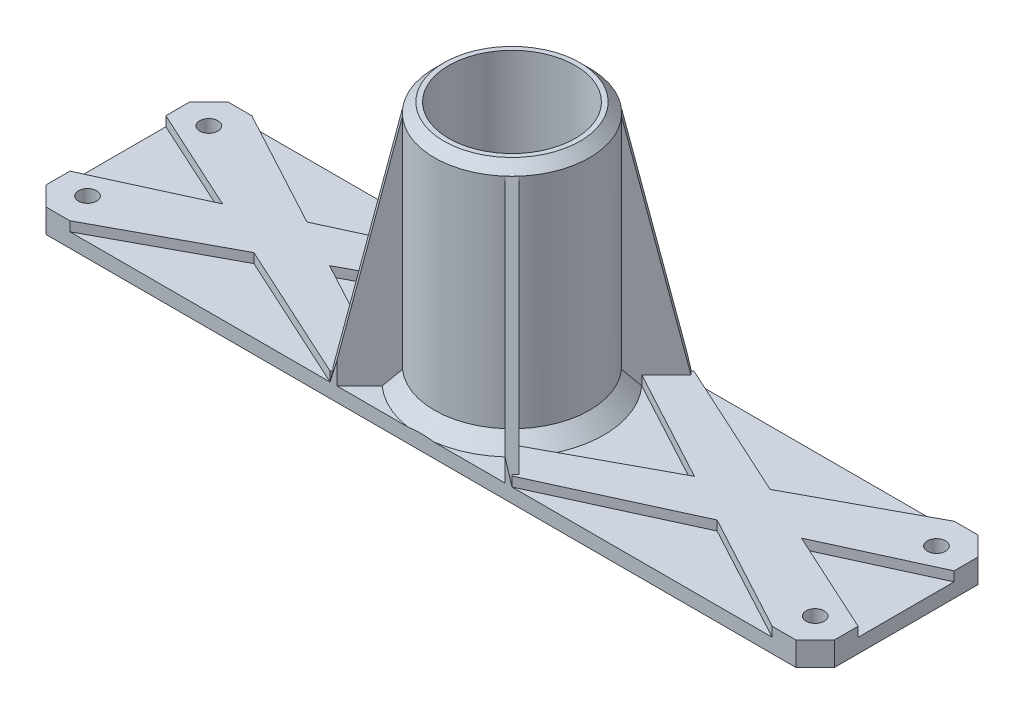
SolidWorks part; units mm, degrees
ref_plane "Front Plane" through (0, 0, 0) normal (0, 0, 1) x (1, 0, 0)
ref_plane "Top Plane" through (0, 0, 0) normal (0, 1, 0) x (1, 0, 0)
ref_plane "Right Plane" through (0, 0, 0) normal (1, 0, 0) x (0, 0, -1)
sketch "Sketch1" plane through (0, 0, 0) normal (0, 1, 0) x (1, 0, 0)
  line L1 (-82.55, 19.05) -> (82.55, 19.05)
  line L2 (-82.55, 19.05) -> (-82.55, -19.05)
  line L3 (-82.55, -19.05) -> (82.55, -19.05)
  line L4 (82.55, 19.05) -> (82.55, -19.05)
  line L5 (-82.55, 19.05) -> (82.55, -19.05) construction
  line L6 (-82.55, -19.05) -> (82.55, 19.05) construction
  point P0 (0, 0)
  dimension "D1" = 38.1
  dimension "D2" = 165.1
extrude "Boss-Extrude1" add sketch "Sketch1" along normal blind 3
sketch "Sketch2" plane through (0, 3, 0) normal (0, 1, 0) x (1, 0, 0)
  line L0 (-82.55, 19.05) -> (-82.55, -19.05) construction
  line L1 (82.55, 19.05) -> (-82.55, 19.05) construction
  line L2 (-82.55, -19.05) -> (82.55, -19.05) construction
  circle A0 centre (-76.2, 12.7) radius 1.9
  circle A1 centre (-76.2, -12.7) radius 1.9
  circle A2 centre (76.2, 12.7) radius 1.9
  circle A3 centre (76.2, -12.7) radius 1.9
  dimension "D1" = 3.8
  dimension "D2" = 25.4
  dimension "D3" = 3.8
  dimension "D4" = 3.8
  dimension "D5" = 3.8
  dimension "D6" = 25.4
  dimension "D7" = 152.4
  dimension "D8" = 152.4
  dimension "D9" = 6.35
  dimension "D10" = 6.35
  dimension "D11" = 6.35
extrude "Cut-Extrude1" cut sketch "Sketch2" against normal blind 3
chamfer "Chamfer1" distance 4 angle 45 4 edges at (-82.55, 1.5, -19.05) (-82.55, 1.5, 19.05) (82.55, 1.5, -19.05) (82.55, 1.5, 19.05)
sketch "Sketch3" plane through (0, 3, 0) normal (0, 1, 0) x (1, 0, 0)
  circle A0 centre (0, 0) radius 13.25
  circle A1 centre (0, 0) radius 16.25
  dimension "D1" = 26.5
  dimension "D2" = 3
extrude "Boss-Extrude2" add sketch "Sketch3" along normal blind 50.8
sketch "Sketch4" plane through (0, 3, 0) normal (0, 1, 0) x (1, 0, 0)
  circle A0 centre (0, 0) radius 9
  dimension "D1" = 18
extrude "Cut-Extrude2" cut sketch "Sketch4" against normal blind 50.8
sketch "Sketch5" plane through (0, 3, 0) normal (0, 1, 0) x (1, 0, 0)
  line L0 (-19.05, 19.05) -> (0, 0) construction
  line L1 (78.55, 19.05) -> (-78.55, 19.05) construction
  line L2 (0, 0) -> (19.05, -19.05) construction
  line L3 (-78.55, -19.05) -> (78.55, -19.05) construction
  line L4 (19.05, 19.05) -> (0, 0) construction
  line L5 (0, 0) -> (-19.05, -19.05) construction
  dimension "D1" = 45
  dimension "D2" = 45
sketch "Sketch6" plane through (0, 0, 0) normal (0, 0, 1) x (1, 0, 0)
  line L0 (0, 0) -> (0, 59.5516) construction
ref_plane "Plane1" through (0, 0, 0) normal (0.7071, 0, 0.7071) x (0.7071, 0, -0.7071)
chamfer "Chamfer2" distance 2 angle 45 1 edges at (0, 53.8, 16.25)
sketch "Sketch8" plane through (0, 0, 0) normal (0.7071, 0, 0.7071) x (0.7071, 0, -0.7071)
  line L0 (-16.25, 51.8) -> (-26.9408, 3)
  line L1 (-26.9408, 3) -> (-15.7619, 3)
  line L3 (-15.7619, 3) -> (-16.25, 51.8)
  line L4 (16.25, 51.8) -> (26.9408, 3)
  line L5 (26.9408, 3) -> (15.6724, 3)
  line L6 (15.6724, 3) -> (16.25, 51.8)
extrude "Boss-Extrude5" add sketch "Sketch8" along normal blind 1 and the other way blind 1
ref_plane "Plane3" through (0, 0, 0) normal (0.7071, 0, -0.7071) x (-0.7071, 0, -0.7071)
sketch "Sketch9" plane through (0, 0, 0) normal (0.7071, 0, -0.7071) x (-0.7071, 0, -0.7071)
  line L0 (26.9408, 3) -> (15.3325, 3)
  line L1 (15.3325, 3) -> (16.038, 52.012)
  line L2 (16.25, 51.8) -> (14.25, 53.8) construction
  line L3 (16.038, 52.012) -> (26.9408, 3)
  line L4 (26.9408, 3) -> (26.9766, 3.0157)
  line L5 (-26.9408, 3) -> (-15.0862, 3)
  line L6 (-15.0862, 3) -> (-16.25, 51.8)
  line L7 (-16.25, 51.8) -> (-26.9408, 3)
extrude "Boss-Extrude6" add sketch "Sketch9" along normal blind 1 and the other way blind 1 contours L3 L1 L0 | L6 L7 L5 region at (-13.7441, 19.3373, -13.7441) region at (13.736, 19.2667, 13.736)
sketch "Sketch10" plane through (0, 0, 0) normal (0, -1, 0) x (1, 0, 0)
  line L0 (-78.55, 19.05) -> (78.55, 19.05) construction
  line L1 (-23.4003, 19.05) -> (24.6276, 19.05)
  line L2 (-23.4003, 19.05) -> (-23.4003, 22.4962)
  line L3 (-23.4003, 22.4962) -> (24.6276, 22.4962)
  line L4 (24.6276, 19.05) -> (24.6276, 22.4962)
  line L5 (78.55, -19.05) -> (-78.55, -19.05) construction
  line L6 (-22.9906, -19.05) -> (22.2393, -19.05)
  line L7 (-22.9906, -19.05) -> (-22.9906, -21.3589)
  line L8 (-22.9906, -21.3589) -> (22.2393, -21.3589)
  line L9 (22.2393, -19.05) -> (22.2393, -21.3589)
extrude "Cut-Extrude3" cut sketch "Sketch10" against normal blind 51
chamfer "Chamfer3" distance 3 angle 45 4 edges at (0, 3, -16.25) (16.25, 3, 0) (0, 3, 16.25) (-16.25, 3, 0)
sketch "Sketch12" plane through (0, 3, 0) normal (0, 1, 0) x (1, 0, 0)
  line L0 (-19.05, 19.05) -> (-48.5063, 5.5511)
  line L1 (-82.55, 15.05) -> (-82.55, -15.05) construction
  line L2 (-82.55, -10.05) -> (-82.55, -15.05)
  line L3 (-82.55, -15.05) -> (-78.55, -19.05)
  line L4 (-78.55, -19.05) -> (-73.55, -19.05)
  line L5 (-78.55, -19.05) -> (-19.05, -19.05) construction
  line L6 (-73.55, -19.05) -> (-48.5063, -5.5511)
  line L7 (-19.05, 19.05) -> (-14.3005, 12.8863)
  line L8 (-14.3005, -12.8863) -> (-38.2077, 0)
  line L9 (-19.05, 19.05) -> (-78.55, 19.05) construction
  line L10 (-73.55, 19.05) -> (-78.55, 19.05)
  line L11 (-78.55, 19.05) -> (-82.55, 15.05)
  line L12 (-82.55, 15.05) -> (-82.55, 10.05)
  line L13 (-82.55, 10.05) -> (-60.6196, 0)
  line L14 (-19.05, -19.05) -> (-14.3005, -12.8863)
  line L15 (14.3005, 12.8863) -> (38.2077, 0)
  line L16 (19.05, -19.05) -> (78.55, -19.05) construction
  line L17 (73.55, -19.05) -> (78.55, -19.05)
  line L18 (78.55, -19.05) -> (82.55, -15.05)
  line L19 (82.55, -15.05) -> (82.55, -10.05)
  line L20 (82.55, -15.05) -> (82.55, 15.05) construction
  line L21 (82.55, -10.05) -> (60.6196, 0)
  line L22 (19.05, 19.05) -> (14.3005, 12.8863)
  line L23 (14.3005, -12.8863) -> (38.2077, 0)
  line L24 (78.55, 19.05) -> (19.05, 19.05) construction
  line L25 (73.55, 19.05) -> (78.55, 19.05)
  line L26 (78.55, 19.05) -> (82.55, 15.05)
  line L27 (82.55, 15.05) -> (82.55, 10.05)
  line L28 (82.55, 10.05) -> (60.6196, 0)
  line L29 (19.05, -19.05) -> (14.3005, -12.8863)
  line L30 (48.5063, 5.5511) -> (19.05, 19.05)
  line L31 (48.5063, -5.5511) -> (73.55, -19.05)
  line L32 (48.5063, 5.5511) -> (73.55, 19.05)
  line L33 (48.5063, -5.5511) -> (19.05, -19.05)
  line L34 (-60.6196, 0) -> (-82.55, -10.05)
  line L35 (-48.5063, -5.5511) -> (-19.05, -19.05)
  line L36 (-38.2077, 0) -> (-14.3005, 12.8863)
  line L37 (-48.5063, 5.5511) -> (-73.55, 19.05)
  circle A0 centre (-76.2, 12.7) radius 1.9
  circle A1 centre (-76.2, -12.7) radius 1.9
  circle A2 centre (76.2, 12.7) radius 1.9
  circle A3 centre (76.2, -12.7) radius 1.9
  dimension "D1" = 5
  dimension "D2" = 5
  dimension "D3" = 5
  dimension "D4" = 5
  dimension "D5" = 5
  dimension "D6" = 5
  dimension "D7" = 5
  dimension "D8" = 5
extrude "Boss-Extrude7" add sketch "Sketch12" along normal blind 2
